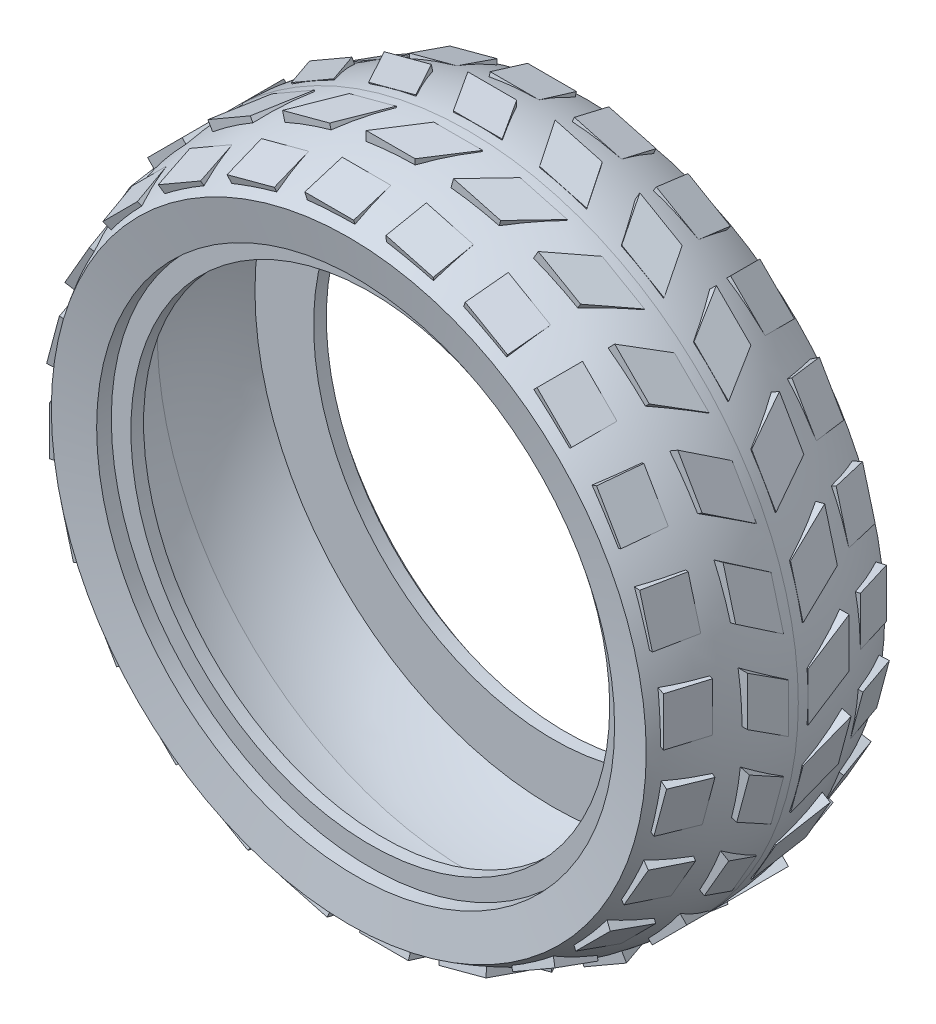
SolidWorks part; units mm, degrees
ref_plane "Front Plane" through (0, 0, 0) normal (0, 0, 1) x (1, 0, 0)
ref_plane "Top Plane" through (0, 0, 0) normal (0, 1, 0) x (1, 0, 0)
ref_plane "Right Plane" through (0, 0, 0) normal (1, 0, 0) x (0, 0, -1)
sketch "Sketch1" plane through (0, 0, 0) normal (1, 0, 0) x (0, 0, -1)
  line L0 (0, -20.4391) -> (0, 35.6896) construction
  line L1 (-17.6584, 0) -> (14.7496, 0) construction
  line L2 (-8.7, 24.5) -> (-10, 24.5)
  line L3 (-10, 24.5) -> (-10, 26.5)
  line L4 (-10, 26.5) -> (-11.5, 26.5)
  line L5 (-8.7, 24.5) -> (-8.7, 30.5)
  line L6 (-11.5, 26.5) -> (-12.2, 30.4383)
  line L7 (8.7, 24.5) -> (10, 24.5)
  line L8 (10, 24.5) -> (10, 26.5)
  line L9 (8.7, 24.5) -> (8.7, 30.5)
  line L10 (10, 26.5) -> (11.5, 26.5)
  line L11 (11.5, 26.5) -> (12.2, 30.4383)
  arc A0 (-8.7, 30.5) -> (0, 31.8) centre (-0.7287, 6.9154) cw
  arc A1 (-12.2, 30.4383) -> (0, 33.8) centre (-0.1518, 10.5324) cw
  arc A2 (8.7, 30.5) -> (0, 31.8) centre (0.7287, 6.9154) ccw
  arc A3 (12.2, 30.4383) -> (0, 33.8) centre (0.1518, 10.5324) ccw
  dimension "D1" = 10
  dimension "D2" = 24.5
  dimension "D3" = 2
  dimension "D4" = 6
  dimension "D5" = 1.3
  dimension "D6" = 1.5
  dimension "D7" = 4
  dimension "D8" = 3.5
  dimension "D9" = 2
  dimension "D10" = 31.8
revolve "Revolve1" add sketch "Sketch1" angle 360 about L1
ref_plane "Plane1" through (33.8, 0, 0) normal (1, 0, 0) x (0, 0, -1)
sketch "Sketch3" plane through (33.8, 0, 0) normal (1, 0, 0) x (0, 0, -1)
  line L0 (-12.8347, 0) -> (12.9227, 0) construction
  line L1 (0, -35.93) -> (0, 37.6227) construction
  line L2 (-1, -2.5) -> (-1, 2.5)
  line L3 (-1, 2.5) -> (-5.2, 5.2129)
  line L4 (-5.2, 5.2129) -> (-5.2, 0.2129)
  line L5 (-5.2, 0.2129) -> (-1, -2.5)
  line L6 (5.2, 0.2129) -> (1, -2.5)
  line L7 (5.2, 5.2129) -> (5.2, 0.2129)
  line L8 (1, -2.5) -> (1, 2.5)
  line L9 (1, 2.5) -> (5.2, 5.2129)
  dimension "D1" = 1
  dimension "D2" = 5
  dimension "D3" = 4.2
  dimension "D4" = 5
  dimension "D5" = 2.5
extrude "Boss-Extrude3" add sketch "Sketch3" against normal up to surface (0.1207 mm away) contours L4 L5 L2 L3 | L9 L8 L6 L7 region at (33.8, 1.3565, 3.1) region at (33.8, 1.3565, -3.1) up to face at (33.8, 0, 0)
pattern_circular "CirPattern1" count 24 over 360 of "Boss-Extrude3"
ref_plane "Plane2" through (33.8, 0, 0) normal (1, 0, 0) x (0, 0, -1)
sketch "Sketch4" plane through (33.8, 0, 0) normal (1, 0, 0) x (0, 0, -1)
  line L0 (-13.0072, 0) -> (13.5074, 0) construction
  line L1 (0, 40.4684) -> (0, -37.9216) construction
ref_plane "Plane3" through (30.9107, 0, 9.4504) normal (0.9563, 0, 0.2924) x (0, -1, 0)
sketch "Sketch5" plane through (30.9107, 0, 9.4504) normal (0.9563, 0, 0.2924) x (0, -1, 0)
  line L0 (-5.3, 2.2822) -> (-0.3, 2.2822)
  line L1 (-40.4684, 9.8822) -> (37.9216, 9.8822) construction
  line L2 (-5.3, 2.2822) -> (-5.3, -1.7178)
  line L3 (-5.3, -1.7178) -> (-0.3, -1.7178)
  line L4 (-0.3, -1.7178) -> (-0.3, 2.2822)
  line L5 (0, 22.7994) -> (0, -5.7747) construction
  dimension "D1" = 5
  dimension "D2" = 4
  dimension "D3" = 7.6
  dimension "D4" = 0.3
extrude "Boss-Extrude5" add sketch "Sketch5" along normal blind 1.05
mirror "Mirror1" about plane through (0, 0, 0) normal (0, 0, 1) of "Boss-Extrude5"
pattern_circular "CirPattern2" count 24 over 360 of "Mirror1", "Boss-Extrude5"
